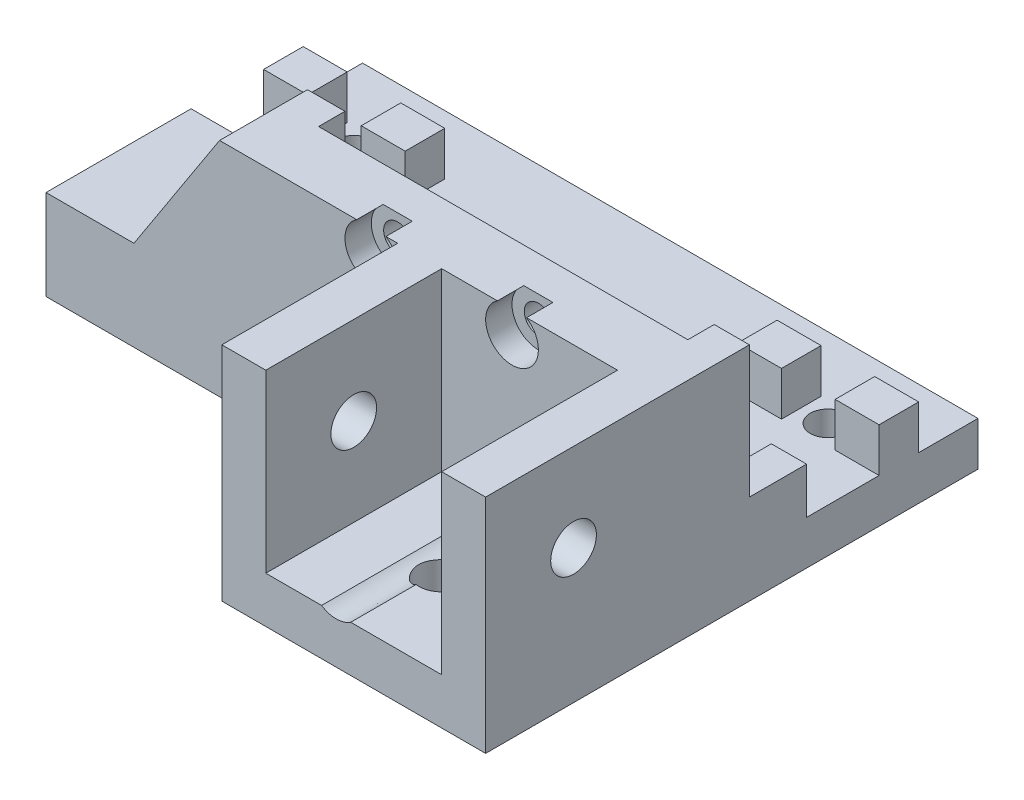
SolidWorks part; units mm, degrees
ref_plane "Front" through (0, 0, 0) normal (0, 0, 1) x (1, 0, 0)
ref_plane "Top" through (0, 0, 0) normal (0, 1, 0) x (1, 0, 0)
ref_plane "Right" through (0, 0, 0) normal (1, 0, 0) x (0, 0, -1)
other "Configuration Table"
sketch "Sketch1" plane through (0, 0, 0) normal (0, 0, 1) x (1, 0, 0)
  line L1 (-20, -10) -> (20, -10)
  line L2 (-20, -10) -> (-20, 10)
  line L3 (-20, 10) -> (20, 10)
  line L4 (20, -10) -> (20, 10)
  line L5 (-20, -10) -> (20, 10) construction
  line L6 (-20, 10) -> (20, -10) construction
  line L7 (-8, -7.5) -> (8, -7.5) construction
  line L8 (-8, -7.5) -> (-8, 7.5) construction
  line L9 (-8, 7.5) -> (8, 7.5) construction
  line L10 (8, -7.5) -> (8, 7.5) construction
  line L11 (-8, -7.5) -> (8, 7.5) construction
  line L12 (-8, 7.5) -> (8, -7.5) construction
  circle A0 centre (-8, 7.5) radius 1.6
  circle A1 centre (8, 7.5) radius 1.6
  circle A2 centre (8, -7.5) radius 1.6
  circle A3 centre (-8, -7.5) radius 1.6
  point P0 (0, 0)
  point P6 (0, 0)
extrude "Boss-Extrude1" add sketch "Sketch1" along normal blind 7
sketch "Sketch2" plane through (20, 0, 0) normal (1, 0, 0) x (0, 0, -1)
  line L0 (0, 0) -> (0, 5) construction
  line L1 (0, -10) -> (0, 10) construction
  line L2 (0, 0) -> (0, -5) construction
  line L3 (0, -5) -> (3, -5) construction
  line L4 (3, -5) -> (3, 5)
  line L5 (3, 5) -> (0, 5) construction
  line L6 (0, -10) -> (9.5, -10)
  line L7 (0, 10) -> (9.5, 10)
  line L8 (9.5, 10) -> (9.5, 5)
  line L9 (9.5, 5) -> (3, 5)
  line L10 (9.5, -10) -> (9.5, -5)
  line L11 (9.5, -5) -> (3, -5)
  line L12 (0, -10) -> (0, -5) construction
  line L13 (0, 5) -> (0, 10) construction
  line L14 (0, -10) -> (-7, -10)
  line L15 (-7, -10) -> (-7, 10)
  line L16 (-7, 10) -> (0, 10)
extrude "Boss-Extrude2" add sketch "Sketch2" along normal blind 5
sketch "Sketch3" plane through (-20, 0, 0) normal (-1, 0, 0) x (0, 0, 1)
  line L0 (7, 10) -> (-9.5, 10)
  line L1 (-9.5, 10) -> (-9.5, 5)
  line L2 (-9.5, 5) -> (-3, 5)
  line L3 (-3, 5) -> (-3, -5)
  line L4 (-3, -5) -> (-9.5, -5)
  line L5 (-9.5, -5) -> (-9.5, -10)
  line L6 (-9.5, -10) -> (7, -10)
  line L7 (7, -10) -> (7, 10)
extrude "Boss-Extrude3" add sketch "Sketch3" along normal blind 5
sketch "Sketch4" plane through (0, -10, 0) normal (0, -1, 0) x (1, 0, 0)
  line L0 (-25, 7) -> (-25, -9.5)
  line L1 (-25, -9.5) -> (-20, -9.5)
  line L2 (-20, -9.5) -> (-20, 0)
  line L3 (-20, 0) -> (20, 0)
  line L4 (20, 0) -> (20, -9.5)
  line L5 (20, -9.5) -> (25, -9.5)
  line L6 (25, -9.5) -> (25, 7)
  line L7 (25, 7) -> (-25, 7)
extrude "Boss-Extrude4" add sketch "Sketch4" along normal blind 0.25
sketch "Sketch5" plane through (0, -10.25, 0) normal (0, -1, 0) x (1, 0, 0)
  line L0 (-20, 0) -> (-20, -29) construction
  line L1 (-25, 7) -> (-25, -29)
  line L2 (25, 7) -> (25, -29)
  line L3 (25, -29) -> (-25, -29)
  line L4 (-25, 7) -> (25, 7)
extrude "Boss-Extrude5" add sketch "Sketch5" along normal blind 5
sketch "Sketch6" plane through (0, 0, 7) normal (0, 0, 1) x (1, 0, 0)
  circle A0 centre (-8, 7.5) radius 3
  circle A1 centre (-8, -7.5) radius 3
  circle A2 centre (8, -7.5) radius 3
  circle A3 centre (8, 7.5) radius 3
extrude "Cut-Extrude1" cut sketch "Sketch6" against normal blind 3
sketch "Sketch7" plane through (-25, 0, 0) normal (-1, 0, 0) x (0, 0, 1)
  line L0 (-3, -5) -> (7, -5)
  line L1 (7, -15.25) -> (7, 10) construction
  line L2 (7, -5) -> (7, -15.25)
  line L3 (7, -15.25) -> (-29, -15.25)
  line L4 (-29, -15.25) -> (-29, -10.25)
  line L5 (-29, -10.25) -> (-9.5, -10.25)
  line L6 (-9.5, -10.25) -> (-9.5, -5)
  line L7 (-9.5, -5) -> (-3, -5)
extrude "Boss-Extrude6" add sketch "Sketch7" along normal blind 20
sketch "Sketch8" plane through (0, -10.25, 0) normal (0, 1, 0) x (1, 0, 0)
  line L0 (20, 20) -> (25, 20) construction
  line L1 (-45, 15.1812) -> (25, 15.1812) construction
  line L2 (20, 0) -> (20, 20) construction
  line L3 (20, 17.75) -> (20, 22.25)
  line L4 (25, 29) -> (25, 9.5) construction
  line L5 (20, 17.75) -> (22, 17.75)
  line L8 (20, 20) -> (13.9, 20) construction
  line L9 (13.9, 20) -> (13.9, 17.75)
  line L10 (13.9, 17.75) -> (11.9, 17.75)
  line L14 (-45, 9.5) -> (-45, 29) construction
  line L15 (-10, 15.1812) -> (-10, 22.1041) construction
  line L16 (-40, 20) -> (-33.9, 20) construction
  line L17 (-40, 20) -> (-45, 20) construction
  line L27 (13.9, 20) -> (13.9, 22.25)
  line L28 (13.9, 22.25) -> (8.9, 22.25)
  line L29 (20, 22.25) -> (25, 22.25)
  line L30 (25, 22.25) -> (25, 17.75)
  line L31 (25, 17.75) -> (22, 17.75)
  line L32 (11.9, 17.75) -> (8.9, 17.75)
  line L33 (8.9, 17.75) -> (8.9, 22.25)
  line L34 (-28.9, 17.75) -> (-28.9, 22.25)
  line L35 (-31.9, 17.75) -> (-28.9, 17.75)
  line L36 (-45, 17.75) -> (-42, 17.75)
  line L37 (-45, 22.25) -> (-45, 17.75)
  line L38 (-40, 22.25) -> (-45, 22.25)
  line L39 (-33.9, 22.25) -> (-28.9, 22.25)
  line L40 (-33.9, 20) -> (-33.9, 22.25)
  line L41 (-33.9, 17.75) -> (-31.9, 17.75)
  line L42 (-33.9, 20) -> (-33.9, 17.75)
  line L43 (-40, 17.75) -> (-42, 17.75)
  line L44 (-40, 17.75) -> (-40, 22.25)
  point P10 (20, 20)
  point P37 (-40, 20)
  dimension "D1" = 20
extrude "Boss-Extrude7" add sketch "Sketch8" along normal blind 5
sketch "Sketch9" plane through (0, 0, 7) normal (0, 0, 1) x (1, 0, 0)
  line L0 (0, 0) -> (20, 0) construction
  line L1 (0, 0) -> (0, 10)
  line L2 (-20, 0) -> (-20, 10) construction
  line L3 (20, 0) -> (20, 10)
  line L4 (-20, 0) -> (-20, -10) construction
  line L5 (20, 0) -> (20, -10)
  line L6 (20, -10) -> (25, -10)
  line L7 (25, 10) -> (25, -15.25) construction
  line L8 (25, -10) -> (25, 10)
  line L9 (25, 10) -> (20, 10)
  line L10 (-20, 10) -> (-25, 10) construction
  line L11 (-25, 10) -> (-25, -10) construction
  line L12 (-25, -10) -> (-20, -10) construction
  line L13 (0, 0) -> (0, -10)
  line L14 (0, 10) -> (-5, 10)
  line L15 (-5, 10) -> (-5, -10)
  line L16 (-5, -10) -> (0, -10)
extrude "Boss-Extrude8" add sketch "Sketch9" along normal blind 20
sketch "Sketch10" plane through (-25, 0, 0) normal (-1, 0, 0) x (0, 0, 1)
  line L0 (0, 0) -> (7, 0) construction
  line L1 (7, 0) -> (7, -5) construction
  line L2 (7, 0) -> (17, 0) construction
  circle A0 centre (17, 0) radius 2.6
extrude "Cut-Extrude2" cut sketch "Sketch10" against normal through all
sketch "Sketch11" plane through (0, 0, 7) normal (0, 0, 1) x (1, 0, 0)
  line L0 (-9.6583, 10) -> (-25, 10) construction
  line L2 (10, -10) -> (10, 10) construction
  line L3 (10, 10) -> (-10, 10) construction
  line L4 (-10, -10) -> (-10, 10) construction
  line L5 (10, -10) -> (-10, 10) construction
  line L6 (10, 10) -> (-10, -10) construction
  line L11 (25, -15.25) -> (25, -10)
  line L12 (25, -10) -> (10, -10)
  line L13 (10, -10) -> (9.6583, -10)
  line L15 (-9.6583, -10) -> (9.6583, -10) construction
  line L17 (6.3417, -10) -> (-5, -10)
  line L18 (-5, -10) -> (-5, -15.25)
  line L19 (25, -15.25) -> (-45, -15.25) construction
  line L20 (-5, -15.25) -> (25, -15.25)
  circle A0 centre (8, -7.5) radius 3 construction
  circle A1 centre (-8, -7.5) radius 3 construction
  circle A2 centre (8, -7.5) radius 3 construction
  spline S0 degree 3 poles (9.6583, -10) (9.1046, -10.3723) (7.8997, -10.6752) (6.7571, -10.2766) (6.3417, -10) knots 0 0 0 0 0.571534 1 1 1 1
  point P0 (0, 0)
extrude "Boss-Extrude9" add sketch "Sketch11" along normal through all
sketch "Sketch12" plane through (0, -15.25, 0) normal (0, -1, 0) x (1, 0, 0)
  line L0 (-5, 17) -> (25, 17) construction
  line L1 (-5, 27) -> (-5, 7) construction
  line L2 (25, -29) -> (25, 27) construction
  circle A0 centre (10, 17) radius 2.6
extrude "Cut-Extrude3" cut sketch "Sketch12" against normal through all
sketch "Sketch13" plane through (0, 0, -9.5) normal (0, 0, -1) x (-1, 0, 0)
  line L1 (20, 10) -> (25, 10)
  line L2 (20, 10) -> (20, 5)
  line L3 (20, 5) -> (25, 5)
  line L4 (25, 10) -> (25, 5)
  line L5 (-20, 5) -> (-25, 5)
  line L6 (-20, 5) -> (-20, 10)
  line L7 (-20, 10) -> (-25, 10)
  line L8 (-25, 5) -> (-25, 10)
extrude "Cut-Extrude4" cut sketch "Sketch13" against normal up to surface (6.5 mm away) up to face at (22.5, 0, -3)
chamfer "Chamfer1" distance 10 angle 57 1 edges at (-25, -5, 2) first distance on face at (-30, -5, -1.8333)
sketch "Sketch14" plane through (0, 0, 0) normal (0, 0, -1) x (-1, 0, 0)
  line L0 (20, 10) -> (21, 10)
  line L1 (25.2589, 10) -> (20, 10) construction
  line L2 (21, 10) -> (21, -10.25)
  line L3 (45, -10.25) -> (20, -10.25) construction
  line L4 (21, -10.25) -> (20, -10.25)
  line L5 (20, -10.25) -> (20, 10)
  line L6 (-20, 10) -> (-21, 10)
  line L7 (-20, 10) -> (-25, 10) construction
  line L8 (-21, 10) -> (-21, -10.25)
  line L9 (45, -10.25) -> (-25, -10.25) construction
  line L10 (-20, -10.25) -> (-25, -10.25) construction
  line L11 (-21, -10.25) -> (-20, -10.25)
  line L12 (-20, -10.25) -> (-20, 10)
extrude "Cut-Extrude5" cut sketch "Sketch14" along normal blind 10
sketch "Sketch15" plane through (0, -10.25, 0) normal (0, 1, 0) x (1, 0, 0)
  line L0 (20, 20) -> (13.9, 19.95) construction
  line L1 (20, 22.25) -> (20, 17.75) construction
  line L3 (-33.9, 19.95) -> (-40, 20) construction
  circle A0 centre (16.95, 19.975) radius 2
  circle A1 centre (-36.95, 19.975) radius 2
extrude "Cut-Extrude6" cut sketch "Sketch15" against normal blind 10
